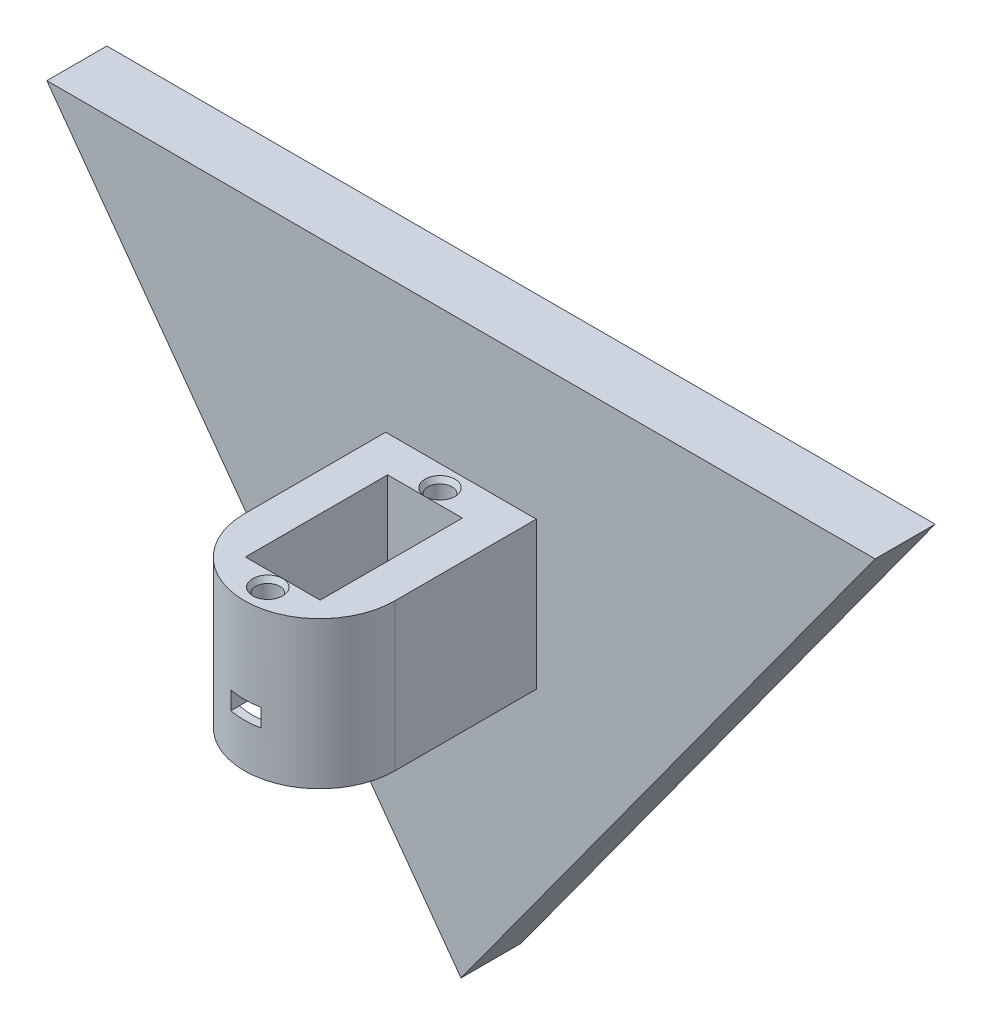
SolidWorks part; units mm, degrees
ref_plane "Front Plane" through (0, 0, 0) normal (0, 0, 1) x (1, 0, 0)
ref_plane "Top Plane" through (0, 0, 0) normal (0, 1, 0) x (1, 0, 0)
ref_plane "Right Plane" through (0, 0, 0) normal (1, 0, 0) x (0, 0, -1)
sketch "Sketch1" plane through (0, 0, 0) normal (0, 0, 1) x (1, 0, 0)
  line L0 (0, 0) -> (54.4907, 75)
  line L1 (54.4907, 75) -> (-54.4907, 75)
  line L2 (-54.4907, 75) -> (0, 0)
  point P10 (0, 75)
  dimension "D2" = 75
  dimension "D1" = 72
extrude "Boss-Extrude1" add sketch "Sketch1" along normal blind 10
sketch "Sketch4" plane through (0, 0, 10) normal (0, 0, 1) x (1, 0, 0)
  line L1 (-6.23, 55.25) -> (6.23, 55.25)
  line L2 (-6.23, 55.25) -> (-6.23, 72.5)
  line L3 (-6.23, 72.5) -> (6.23, 72.5)
  line L4 (6.23, 55.25) -> (6.23, 72.5)
  point P4 (0, 72.5)
  dimension "D1" = 12.46
  dimension "D2" = 17.25
extrude "Boss-Extrude3" add sketch "Sketch4" along normal blind 6
sketch "Sketch8" plane through (0, 55.25, 0) normal (0, -1, 0) x (-1, 0, 0)
  circle A0 centre (0, -33.55) radius 12.5468
  circle A1 centre (0, -33.55) radius 11.15
  dimension "D1" = 22.3
  dimension "D3" = 23.55
extrude "Boss-Extrude6" add sketch "Sketch8" along normal blind 7.3 and the other way up to surface (17.25 mm away) other way up to face at (0, 72.5, 13)
sketch "Sketch5" plane through (0, 72.5, 0) normal (0, 1, 0) x (1, 0, 0)
  line L8 (12.5468, -33.55) -> (12.5468, -10)
  line L9 (12.5468, -10) -> (6.23, -10)
  line L10 (-12.5468, -33.55) -> (-12.5468, -10)
  line L11 (-12.5468, -10) -> (-6.23, -10)
  line L12 (-6.23, -10) -> (-6.23, -39.7)
  line L14 (6.23, -39.7) -> (6.23, -10)
  line L15 (-6.23, -39.7) -> (6.23, -39.7)
  line L16 (6.23, -16) -> (-6.23, -16) construction
  circle A0 centre (0, -33.55) radius 12.5468 construction
  arc A1 (-12.5468, -33.55) -> (12.5468, -33.55) centre (0, -33.55) ccw
  dimension "D1" = 23.7
  dimension "D2" = 23.55
extrude "Boss-Extrude4" add sketch "Sketch5" against normal up to surface (17.25 mm away) up to face at (0, 55.25, 13)
sketch "Sketch6" plane through (0, 72.5, 0) normal (0, 1, 0) x (1, 0, 0)
  line L0 (6.23, -16) -> (-6.23, -16) construction
  line L3 (6.23, -39.7) -> (-6.23, -39.7) construction
  circle A0 centre (0, -13.5) radius 2
  circle A1 centre (0, -42.2) radius 2
  dimension "D1" = 4
  dimension "D3" = 4
  dimension "D2" = 2.5
  dimension "D4" = 2.5
extrude "Cut-Extrude1" cut sketch "Sketch6" against normal blind 5
chamfer "Chamfer1" distance 0.5 angle 60 2 edges at (0, 72.5, 15.5) (0, 72.5, 44.2) first distance on face at (0, 72.5, 15.5)
sketch "Sketch2" plane through (0, 0, 0) normal (0, 0, 1) x (1, 0, 0)
  line L0 (-54.4907, 75) -> (-69.0215, 95)
  line L1 (-69.0215, 95) -> (69.0215, 95)
  line L2 (69.0215, 95) -> (54.4907, 75)
  line L3 (54.4907, 75) -> (-54.4907, 75)
  line L4 (-54.4907, 75) -> (0, 0) construction
  line L5 (0, 0) -> (54.4907, 75) construction
  dimension "D1" = 180
  dimension "D2" = 180
  dimension "D3" = 20
extrude "Boss-Extrude2" add sketch "Sketch2" along normal blind 10
sketch "Sketch10" plane through (0, 72.5, 0) normal (0, 1, 0) x (1, 0, 0)
  line L1 (-6.23, -16) -> (6.23, -16)
  line L2 (-6.23, -16) -> (-6.23, -39.7)
  line L3 (-6.23, -39.7) -> (6.23, -39.7)
  line L4 (6.23, -16) -> (6.23, -39.7)
extrude "Cut-Extrude3" cut sketch "Sketch10" against normal up to surface (17.25 mm away) up to face at (0, 55.25, 37.1007)
ref_plane "Plane1" through (0, 0, 46.0968) normal (0, 0, 1) x (1, 0, 0)
sketch "Sketch11" plane through (0, 0, 46.0968) normal (0, 0, 1) x (1, 0, 0)
  line L0 (-11.15, 55.25) -> (11.15, 55.25) construction
  line L1 (-2.5, 58.25) -> (2.5, 58.25)
  line L2 (-2.5, 58.25) -> (-2.5, 55.25)
  line L3 (-2.5, 55.25) -> (2.5, 55.25)
  line L4 (2.5, 58.25) -> (2.5, 55.25)
  point P4 (0, 58.25)
  dimension "D1" = 0
  dimension "D2" = 5
  dimension "D3" = 3
extrude "Cut-Extrude4" cut sketch "Sketch11" against normal up to next
sketch "Sketch13" plane through (0, 47.95, 0) normal (0, -1, 0) x (1, 0, 0)
  line L0 (-12.5468, 33.55) -> (-12.5468, 10)
  line L1 (-12.5468, 10) -> (12.5468, 10)
  line L2 (12.5468, 10) -> (12.5468, 33.55)
  arc A0 (-12.5468, 33.55) -> (12.5468, 33.55) centre (0, 33.55) ccw
extrude "Boss-Extrude7" add sketch "Sketch13" against normal up to surface (7.3 mm away) up to face at (-6.0145, 55.25, 37.3356)
